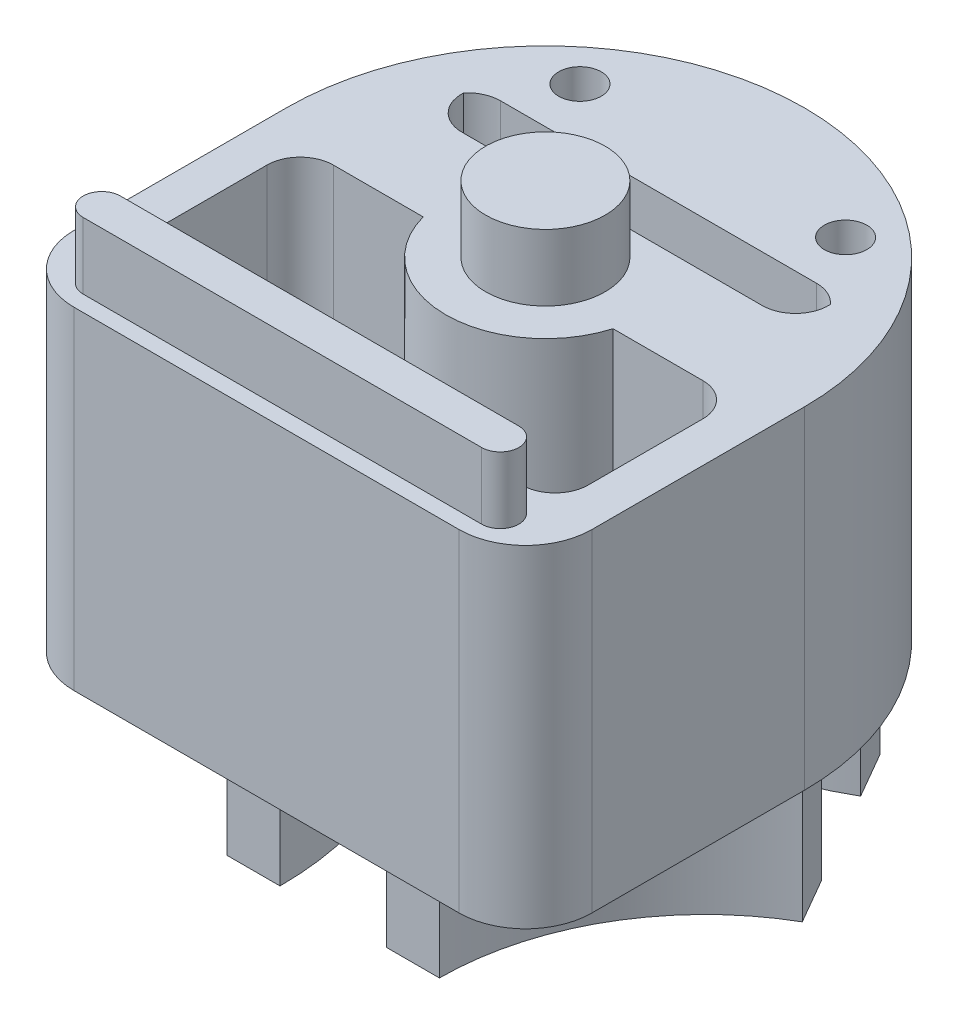
SolidWorks part; units mm, degrees
ref_plane "Front Plane" through (0, 0, 0) normal (0, 0, 1) x (1, 0, 0)
ref_plane "Top Plane" through (0, 0, 0) normal (0, 1, 0) x (1, 0, 0)
ref_plane "Right Plane" through (0, 0, 0) normal (1, 0, 0) x (0, 0, -1)
sketch "Sketch1" plane through (0, 0, 0) normal (0, 1, 0) x (1, 0, 0)
  circle A0 centre (0, 0) radius 28
  circle A1 centre (-28, -48.4974) radius 28
  circle A2 centre (28, -48.4974) radius 28
  arc A3 (-4.6726, -29.6339) -> (4.6726, -29.6339) centre (0, 0) ccw
  arc A4 (0, -37.7271) -> (-4.6726, -29.6339) centre (-28, -48.4974) ccw
  arc A5 (4.6726, -29.6339) -> (0, -37.7271) centre (28, -48.4974) ccw
  circle A6 centre (0, 0) radius 30 construction
  circle A7 centre (-28, -48.4974) radius 30 construction
  circle A8 centre (28, -48.4974) radius 30 construction
  circle A9 centre (0, 0) radius 24
  circle A10 centre (-28, -48.4974) radius 24
  circle A11 centre (28, -48.4974) radius 24
  circle A12 centre (0, 0) radius 20
  circle A13 centre (-28, -48.4974) radius 20
  circle A14 centre (28, -48.4974) radius 20
  dimension "D1" = 56
  dimension "D2" = 2
  dimension "D3" = 4
  dimension "D4" = 4
extrude "Boss-Extrude1" add sketch "Sketch1" along normal blind 10 contours A10 A13 | A9 A12 | A11 A14 | A5 A3 A4 region at (0, 0, 32.3316) region at (-23.3212, 0, 0) region at (-51.3212, 0, 48.4974) region at (4.6788, 0, 48.4974)
sketch "Sketch2" plane through (0, 10, 0) normal (0, 1, 0) x (1, 0, 0)
  line L0 (-19.5, -32.517) -> (-19.5, -53.517)
  line L1 (-19.5, -53.517) -> (19.5, -53.517)
  line L2 (19.5, -53.517) -> (19.5, -32.517)
  arc A0 (19.5, -32.517) -> (-19.5, -32.517) centre (0, -32.517) ccw
  dimension "D1" = 39
  dimension "D2" = 21
extrude "Boss-Extrude2" add sketch "Sketch2" along normal blind 25
sketch "Sketch3" plane through (0, 0, 0) normal (0, -1, 0) x (1, 0, 0)
  line L0 (0, 0) -> (28, 48.4974)
  line L1 (28, 48.4974) -> (-28, 48.4974)
  line L2 (-28, 48.4974) -> (0, 0)
  line L4 (-59.3942, 74.2986) -> (61.8263, 74.2986)
  line L5 (-59.3942, 74.2986) -> (-59.3942, -27.4652)
  line L6 (-59.3942, -27.4652) -> (61.8263, -27.4652)
  line L7 (61.8263, 74.2986) -> (61.8263, -27.4652)
  circle A0 centre (-28, 48.4974) radius 20 construction
  circle A1 centre (28, 48.4974) radius 20 construction
extrude "Cut-Extrude1" cut sketch "Sketch3" against normal blind 10
sketch "Sketch4" plane through (0, 35, 0) normal (0, 1, 0) x (1, 0, 0)
  line L0 (-10, -19.917) -> (10, -19.917) construction
  line L1 (-10, -18.317) -> (10, -18.317)
  line L2 (-10, -21.517) -> (10, -21.517)
  line L3 (-15, -50.917) -> (15, -50.917) construction
  line L4 (-15, -49.517) -> (15, -49.517)
  line L5 (-15, -52.317) -> (15, -52.317)
  circle A0 centre (0, -32.517) radius 4.5
  arc A1 (-10, -18.317) -> (-10, -21.517) centre (-10, -19.917) ccw
  arc A2 (10, -21.517) -> (10, -18.317) centre (10, -19.917) ccw
  arc A3 (-15, -49.517) -> (-15, -52.317) centre (-15, -50.917) ccw
  arc A4 (15, -52.317) -> (15, -49.517) centre (15, -50.917) ccw
  circle A5 centre (0, -32.517) radius 19.5 construction
  circle A6 centre (-10, -19.917) radius 1.6
  circle A7 centre (10, -19.917) radius 1.6
  circle A8 centre (-15, -50.917) radius 1.4
  circle A9 centre (15, -50.917) radius 1.4
  point P4 (0, -19.917)
  point P9 (0, -50.917)
  dimension "D1" = 9
  dimension "D2" = 12.6
  dimension "D3" = 3.2
  dimension "D4" = 20
  dimension "D5" = 2.8
  dimension "D6" = 30
  dimension "D7" = 18.4
sketch "Sketch5" plane through (0, 35, 0) normal (0, 1, 0) x (1, 0, 0)
  line L7 (-13.596, -24) -> (13.596, -24)
  line L8 (13.596, -24) -> (15, -27.5)
  line L9 (15, -27.5) -> (-15, -27.5)
  line L10 (-15, -27.5) -> (-13.596, -24)
  arc A1 (-12, -20.7846) -> (12, -20.7846) centre (0, 0) ccw construction
  point P16 (-12.4447, -33.6914)
  dimension "D3" = 3.5
extrude "Cut-Extrude2" cut sketch "Sketch5" against normal up to surface (25 mm away) up to face at (-10.2237, 10, 38.2343)
fillet "Fillet2" radius 2.5 4 edges at (15, 22.5, 27.5) (-15, 22.5, 27.5) (13.596, 22.5, 24) (-13.596, 22.5, 24)
sketch "Sketch6" plane through (0, 10, 0) normal (0, -1, 0) x (1, 0, 0)
  line L1 (-9.9783, 39.8246) -> (-16.0405, 43.3246)
  line L2 (-11.4783, 37.2265) -> (-17.5405, 40.7265)
  line L3 (-16.0405, 43.3246) -> (-17.5405, 40.7265)
  line L6 (-9.9783, 39.8246) -> (-9.3884, 39.4841)
  line L7 (-11.4783, 37.2265) -> (-10.8884, 36.886)
  line L8 (-9.3884, 39.4841) -> (-10.8884, 36.886)
  line L9 (-10.1384, 38.185) -> (-7.2154, 36.4974)
  arc A0 (-18, 31.1769) -> (-8, 48.4974) centre (-28, 48.4974) ccw construction
  arc A1 (-16, 27.7128) -> (-4, 48.4974) centre (-28, 48.4974) ccw construction
  arc A2 (-18, 31.1769) -> (-8, 48.4974) centre (-28, 48.4974) ccw construction
  point P13 (-10.7283, 38.5256)
  dimension "D1" = 3
  dimension "D2" = 7
extrude "Boss-Extrude5" add sketch "Sketch6" along normal blind 7.5 contours L2 L3 L1 L6 L8 L7
chamfer "Chamfer1" distance 7.5 angle 43 1 edges at (-16.7905, 2.5, 42.0256) first distance on face at (-16.7905, 6.25, 42.0256)
ref_plane "Plane1" through (0, 0, 0) normal (-1, 0, 0) x (0, 0, 1)
mirror "Mirror1" about plane through (0, 0, 0) normal (-1, 0, 0) of "Chamfer1", "Boss-Extrude5"
sketch "Sketch7" plane through (0, 10, 0) normal (0, -1, 0) x (-1, 0, 0)
  line L0 (1.5, -20.1744) -> (-1.5, -20.1744)
  line L1 (1.5, -20.1744) -> (1.5, -13.1744)
  line L2 (-1.5, -20.1744) -> (-1.5, -13.1744)
  line L3 (1.5, -13.1744) -> (-1.5, -13.1744)
  arc A0 (19.5, -32.517) -> (-19.5, -32.517) centre (0, -32.517) ccw construction
  point P0 (0, -20.1744)
  point P3 (0, -13.017)
  point P6 (0, 0)
  dimension "D1" = 3
  dimension "D2" = 7
extrude "Boss-Extrude6" add sketch "Sketch7" along normal blind 7.5
chamfer "Chamfer2" distance 7 angle 45 1 edges at (0, 2.5, 13.1744)
fillet "Fillet4" radius 5 2 edges at (19.5, 22.5, 53.517) (-19.5, 22.5, 53.517)
extrude "Boss-Extrude7" add sketch "Sketch4" along normal blind 5 contours A0
extrude "Cut-Extrude3" cut sketch "Sketch4<3>" against normal blind 15 contours A1 A6 | A2 A7 region at (-10, 35, 19.917) region at (10, 35, 19.917)
sketch "Sketch4<3>" plane through (0, 35, 0) normal (0, 1, 0) x (1, 0, 0) same geometry as "Sketch4"
sketch "Sketch8" plane through (0, 35, 0) normal (0, 1, 0) x (1, 0, 0)
  line L0 (-16.5, -34.4823) -> (-16.5, -48.2559)
  line L1 (-16.5, -48.2559) -> (16.4594, -48.2559)
  line L2 (16.4594, -48.2559) -> (16.4594, -34.6262)
  line L3 (16.4594, -34.6262) -> (7.1973, -34.6262)
  line L4 (-16.5, -34.4823) -> (-7.2379, -34.4823)
  line L5 (-19.5, -32.517) -> (-19.5, -48.517) construction
  arc A0 (-7.2379, -34.4823) -> (7.1973, -34.6262) centre (0, -32.517) ccw
  point P8 (-16.8155, -34.7175)
  dimension "D2" = 7.5
  dimension "D1" = 3
extrude "Cut-Extrude4" cut sketch "Sketch8" against normal blind 21
fillet "Fillet5" radius 2.5 4 edges at (16.4594, 24.5, 34.6262) (16.4594, 24.5, 48.2559) (-16.5, 24.5, 48.2559) (-16.5, 24.5, 34.4823)
sketch "Sketch9" plane through (0, 14, 0) normal (0, 1, 0) x (1, 0, 0)
  line L0 (-1.5, -48.2559) -> (1.5, -48.2559)
  line L1 (-1.5, -48.2559) -> (-1.5, -39.4989)
  line L2 (1.5, -48.2559) -> (1.5, -39.4989)
  line L3 (-1.5, -39.4989) -> (1.5, -39.4989)
  line L4 (-14, -48.2559) -> (13.9594, -48.2559) construction
  line L5 (-14, -48.2559) -> (13.9594, -48.2559) construction
  point P8 (0, -32.517)
  point P9 (0, -39.4989)
  point P11 (0, 0)
  dimension "D1" = 3
extrude "Boss-Extrude8" add sketch "Sketch9" along normal blind 10
extrude "Boss-Extrude10" add sketch "Sketch4<5>" along normal blind 5 contours A9 L4 A8 L5 | A4 A9 | A8 region at (0, 35, 50.917) region at (15, 35, 50.917)
sketch "Sketch4<5>" plane through (0, 35, 0) normal (0, 1, 0) x (1, 0, 0) same geometry as "Sketch4"
